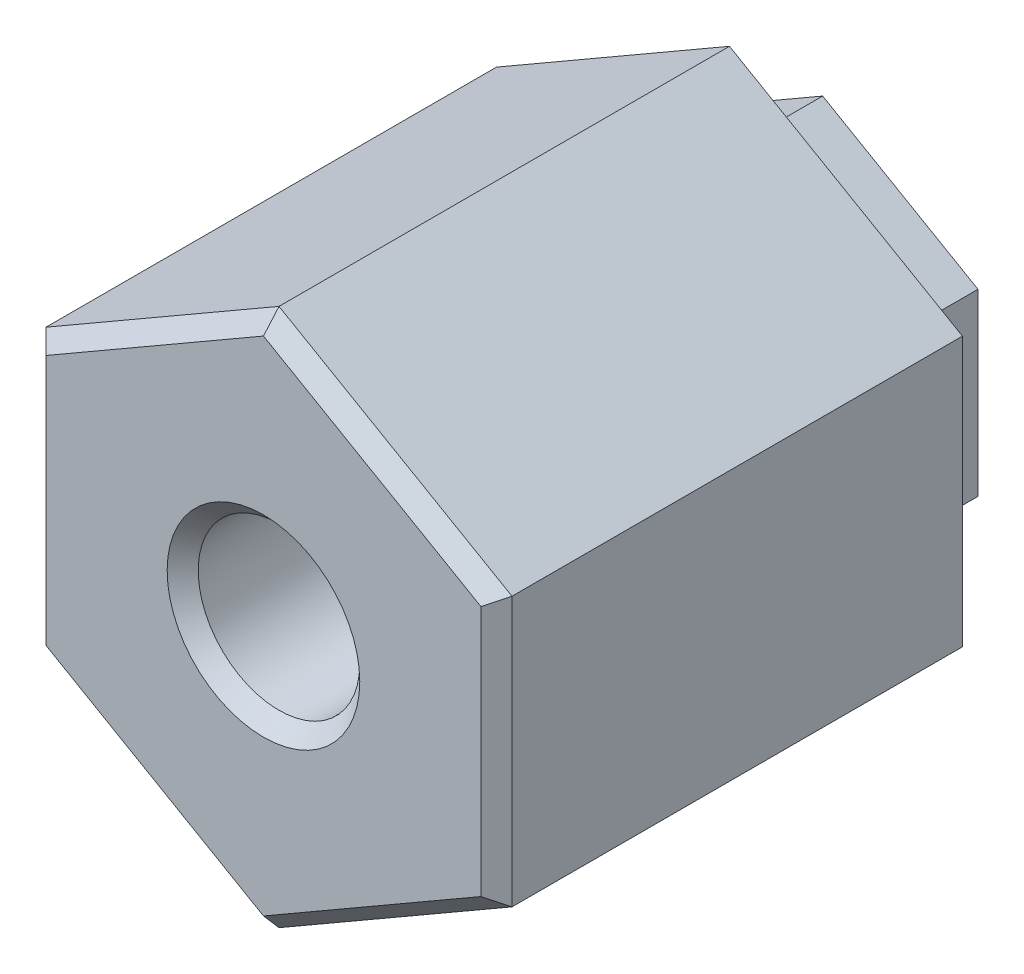
SolidWorks part; units mm, degrees
ref_plane "Front" through (0, 0, 0) normal (0, 0, 1) x (1, 0, 0)
ref_plane "Top" through (0, 0, 0) normal (0, 1, 0) x (1, 0, 0)
ref_plane "Right" through (0, 0, 0) normal (1, 0, 0) x (0, 0, -1)
sketch "Sketch1" plane through (0, 0, 0) normal (0, 0, 1) x (1, 0, 0)
  line L1 (0, 8.6603) -> (-7.5, 4.3301)
  line L2 (-7.5, 4.3301) -> (-7.5, -4.3301)
  line L3 (-7.5, -4.3301) -> (0, -8.6603)
  line L4 (0, -8.6603) -> (7.5, -4.3301)
  line L5 (7.5, -4.3301) -> (7.5, 4.3301)
  line L6 (7.5, 4.3301) -> (0, 8.6603)
  circle A0 centre (0, 0) radius 7.5 construction
  dimension "D1" = 15
extrude "Boss-Extrude1" add sketch "Sketch1" along normal blind 15
sketch "Sketch3" plane through (0, 0, 0) normal (0, 0, -1) x (-1, 0, 0)
  line L0 (-7.5, 4.3301) -> (0, 8.6603) construction
  line L1 (0, 5.7735) -> (-5, 2.8868)
  line L2 (-5, 2.8868) -> (-5, -2.8868)
  line L3 (-5, -2.8868) -> (0, -5.7735)
  line L4 (0, -5.7735) -> (5, -2.8868)
  line L5 (5, -2.8868) -> (5, 2.8868)
  line L6 (5, 2.8868) -> (0, 5.7735)
  circle A0 centre (0, 0) radius 5 construction
  dimension "D1" = 10
extrude "Boss-Extrude2" add sketch "Sketch3" along normal blind 3
sketch "Sketch2" plane through (0, 0, 15) normal (0, 0, 1) x (1, 0, 0)
  circle A0 centre (0, 0) radius 2.6
  dimension "D1" = 5.2
extrude "Cut-Extrude1" cut sketch "Sketch2" against normal through all
sketch "Sketch4" plane through (3.75, 6.4952, 0) normal (0.5, 0.866, 0) x (0.866, -0.5, 0)
  line L0 (4.3301, 0) -> (-4.3301, 0) construction
  circle A0 centre (0, -10) radius 1.5
  point P5 (0, 0)
  dimension "D1" = 3
  dimension "D2" = 10
ref_axis "Axis1" through (0, 0, -3) along (0, 0, 1)
chamfer "Chamfer1" distance 0.5 angle 45 7 edges at (7.5, 0, 15) (3.75, -6.4952, 15) (-3.75, -6.4952, 15) (-7.5, 0, 15) (-3.75, 6.4952, 15) (3.75, 6.4952, 15) (2.6, 0, 15)
